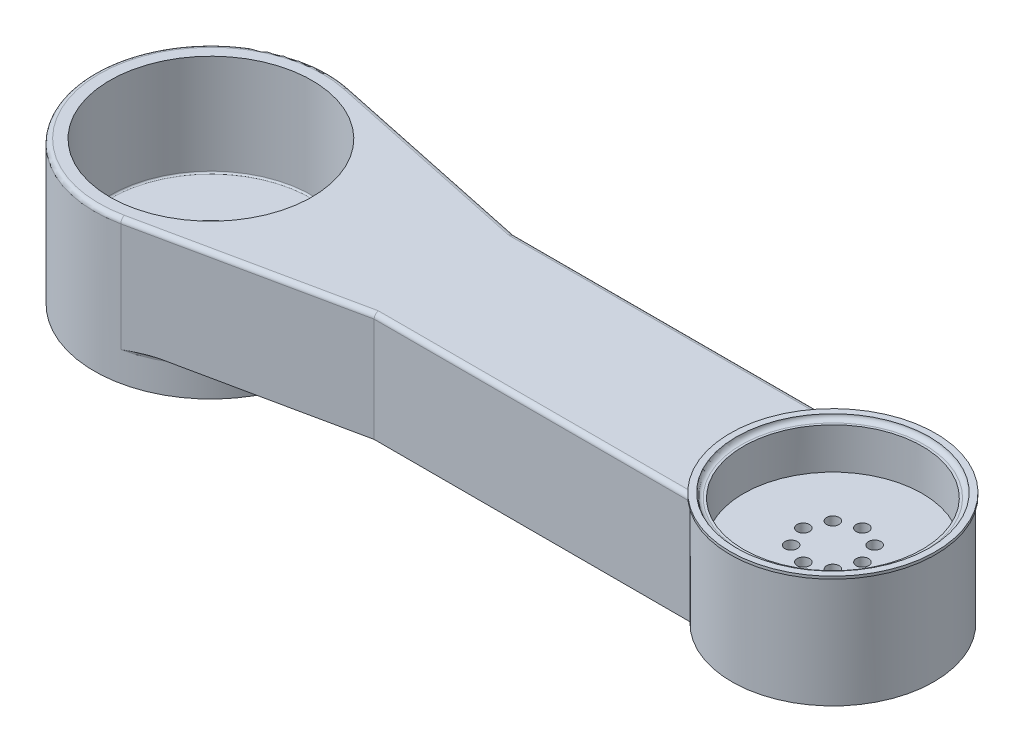
SolidWorks part; units mm, degrees
material "Gray Cast Iron"
ref_plane "Front Plane" through (0, 0, 0) normal (0, 0, 1) x (1, 0, 0)
ref_plane "Top Plane" through (0, 0, 0) normal (0, 1, 0) x (1, 0, 0)
ref_plane "Right Plane" through (0, 0, 0) normal (1, 0, 0) x (0, 0, -1)
other "Center of Mass"
sketch "Sketch1" plane through (0, 0, 0) normal (0, 1, 0) x (1, 0, 0)
  line L0 (150, 45) -> (15.4848, 73.3841)
  line L1 (150, 45) -> (353.0958, 45)
  line L2 (15.4848, -73.3841) -> (150, -45)
  line L3 (150, -45) -> (353.0958, -45)
  arc A0 (15.4848, 73.3841) -> (15.4848, -73.3841) centre (0, 0) ccw
  arc A1 (353.0958, -45) -> (353.0958, 45) centre (400, 0) ccw
  dimension "D1" = 150
  dimension "D2" = 130
  dimension "D3" = 400
  dimension "D4" = 90
  dimension "D5" = 150
extrude "Boss-Extrude1" add sketch "Sketch1" along normal blind 70
sketch "Sketch2" plane through (0, 0, 0) normal (0, -1, 0) x (1, 0, 0)
  circle A0 centre (0, 0) radius 75
  circle A1 centre (0, 0) radius 65
  dimension "D1" = 130
  dimension "D2" = 150
extrude "Boss-Extrude2" add sketch "Sketch2" along normal blind 22
fillet "Fillet1" radius 2 1 edges at (0, 0, -65)
ref_axis "Axis1" through (0, 154.6029, 0) along (0, -1, 0)
sketch "Sketch3" plane through (0, 0, 0) normal (0, 0, 1) x (1, 0, 0)
  line L0 (0, 70) -> (0, 5)
  line L1 (0, 70) -> (65, 70)
  line L2 (0, 5) -> (13, 5)
  line L3 (65, 70) -> (65, 6)
  line L4 (0, 154.6029) -> (0, -118.4497) construction
  line L5 (15.4848, 70) -> (150, 70) construction
  line L6 (14, 6.5) -> (25.5, 6.5)
  line L7 (25.5, 6.5) -> (25.5, 6)
  line L8 (14, 6.5) -> (14, 6)
  line L9 (26.5, 5) -> (64, 5)
  arc A0 (13, 5) -> (14, 6) centre (13, 6) ccw
  arc A1 (26.5, 5) -> (25.5, 6) centre (26.5, 6) cw
  arc A2 (64, 5) -> (65, 6) centre (64, 6) ccw
  point P17 (25.5, 5)
  point P20 (65, 5)
  dimension "D6" = 1
  dimension "D7" = 1
  dimension "D8" = 1
  dimension "D1" = 65
  dimension "D2" = 65
  dimension "D3" = 11.5
  dimension "D4" = 1.5
  dimension "D5" = 25.5
revolve "Cut-Revolve1" cut sketch "Sketch3" angle 360 about axis through (0, 154.6029, 0) along (0, -1, 0)
sketch "Sketch4" plane through (0, 6.5, 0) normal (0, 1, 0) x (1, 0, 0)
  circle A0 centre (19, 0) radius 4
  circle A1 centre (13.435, -13.435) radius 4
  circle A2 centre (0, -19) radius 4
  circle A3 centre (-13.435, -13.435) radius 4
  circle A4 centre (-19, 0) radius 4
  circle A5 centre (-13.435, 13.435) radius 4
  circle A6 centre (0, 19) radius 4
  circle A7 centre (13.435, 13.435) radius 4
  point P20 (0, 0)
  dimension "D1" = 8
  dimension "D2" = 19
  dimension "D3" = 8
extrude "Cut-Extrude1" cut sketch "Sketch4" against normal through all
ref_axis "Axis2" through (400, 150.1784, 0) along (0, -1, 0)
sketch "Sketch5" plane through (0, 0, 0) normal (0, 0, 1) x (1, 0, 0)
  line L0 (400, 0) -> (400, 36.66)
  line L1 (400, 0) -> (459.5, 0)
  line L2 (400, 36.66) -> (413, 36.66)
  line L3 (459.5, 0) -> (459.5, 35.66)
  line L4 (400, 150.1784) -> (400, -67.71) construction
  line L5 (353.0958, 0) -> (465, 0) construction
  line L6 (414, 35.16) -> (425.5, 35.16)
  line L7 (414, 35.16) -> (414, 35.66)
  line L8 (425.5, 35.16) -> (425.5, 35.66)
  line L9 (426.5, 36.66) -> (458.5, 36.66)
  arc A0 (414, 35.66) -> (413, 36.66) centre (413, 35.66) ccw
  arc A1 (426.5, 36.66) -> (425.5, 35.66) centre (426.5, 35.66) ccw
  arc A2 (459.5, 35.66) -> (458.5, 36.66) centre (458.5, 35.66) ccw
  point P16 (425.5, 36.66)
  point P19 (459.5, 36.66)
  dimension "D6" = 1
  dimension "D7" = 1
  dimension "D8" = 1
  dimension "D1" = 59.5
  dimension "D2" = 36.66
  dimension "D3" = 11.5
  dimension "D4" = 1.5
  dimension "D5" = 25.5
revolve "Cut-Revolve2" cut sketch "Sketch5" angle 360 about axis through (400, 150.1784, 0) along (0, -1, 0)
sketch "Sketch6" plane through (0, 35.16, 0) normal (0, -1, 0) x (1, 0, 0)
  circle A0 centre (419, 0) radius 4
  dimension "D1" = 8
  dimension "D2" = 19
extrude "Cut-Extrude2" cut sketch "Sketch6" against normal through all
pattern_circular "CirPattern1" count 8 over 360 about axis through (400, 150.1784, 0) along (0, -1, 0) of "Cut-Extrude2"
sketch "Sketch7" plane through (0, 70, 0) normal (0, 1, 0) x (1, 0, 0)
  circle A0 centre (400, 0) radius 57.5
  dimension "D1" = 115
extrude "Cut-Extrude3" cut sketch "Sketch7" against normal offset from surface (26.34 mm away) 7 up to face at (400, 36.66, 26.5)
sketch "Sketch8" plane through (0, 0, 0) normal (0, -1, 0) x (1, 0, 0)
  line L0 (62.2824, 56.3552) -> (149.2695, 38)
  line L12 (14.0395, 66.5349) -> (149.2695, 38)
  line L13 (149.2695, 38) -> (353.0958, 38)
  line L15 (149.2695, 38) -> (341.6991, 38)
  line L19 (353.0958, -38) -> (149.2695, -38)
  line L20 (149.2695, -38) -> (14.0395, -66.5349)
  line L21 (341.6991, -38) -> (149.2695, -38)
  line L22 (149.2695, -38) -> (62.2824, -56.3552)
  arc A0 (57.4219, -48.2465) -> (57.4219, 48.2465) centre (0, 0) ccw
  arc A1 (344.2712, 33.4559) -> (344.2712, -33.4559) centre (400, 0) ccw
  arc A2 (62.2824, 56.3552) -> (57.4219, 48.2465) centre (61.2501, 51.4629) ccw
  arc A3 (57.4219, -48.2465) -> (62.2824, -56.3552) centre (61.2501, -51.4629) ccw
  arc A4 (341.6991, -38) -> (344.2712, -33.4559) centre (341.6991, -35) ccw
  arc A5 (344.2712, 33.4559) -> (341.6991, 38) centre (341.6991, 35) ccw
  dimension "D3" = 5
  dimension "D4" = 10
  dimension "D5" = 150
  dimension "D6" = 130
  dimension "D7" = 6
  dimension "D8" = 6
  dimension "D1" = 7
  dimension "D2" = 7
extrude "Cut-Extrude4" cut sketch "Sketch8" against normal blind 57
fillet "Fillet2" radius 7 2 edges at (149.2695, 28.5, -38) (149.2695, 28.5, 38)
fillet "Fillet3" radius 5 12 edges at (335, 57, 0) (344.3098, 57, -36.4778) (245.8495, 57, -38) (149.2735, 57, -38.0378) (105.4186, 57, -47.253) (56.9615, 57, -54.0335) (75, 57, 0) (56.9615, 57, 54.0335) (105.4186, 57, 47.253) (149.2735, 57, 38.0378) (245.8495, 57, 38) (344.3098, 57, 36.4778)
sketch "Sketch9" plane through (0, 0, 0) normal (0, 0, 1) x (1, 0, 0)
  line L0 (462, 73) -> (462, 70)
  line L1 (465, 70) -> (353.0958, 70) construction
  line L2 (462, 70) -> (465, 70)
  line L3 (465, 70) -> (465, 71.3)
  line L4 (465, 71.3) -> (466, 71.3)
  line L5 (466, 71.3) -> (466, 73)
  line L6 (466, 73) -> (462, 73)
  line L7 (400, 150.1784) -> (400, -67.71) construction
  dimension "D1" = 4
  dimension "D2" = 1
  dimension "D3" = 3
  dimension "D4" = 1.7
  dimension "D5" = 65
revolve "Revolve1" add sketch "Sketch9" angle 360 about axis through (400, 150.1784, 0) along (0, -1, 0)
fillet "Fillet4" radius 3 1 edges at (400, 70, 62)
fillet "Fillet5" radius 3 7 edges at (82.7424, 70, -59.192) (-75, 70, 0) (38.5593, 0, -64.3287) (38.5593, 0, 64.3287) (251.5479, 70, -45) (82.7424, 70, 59.192) (251.5479, 70, 45)
